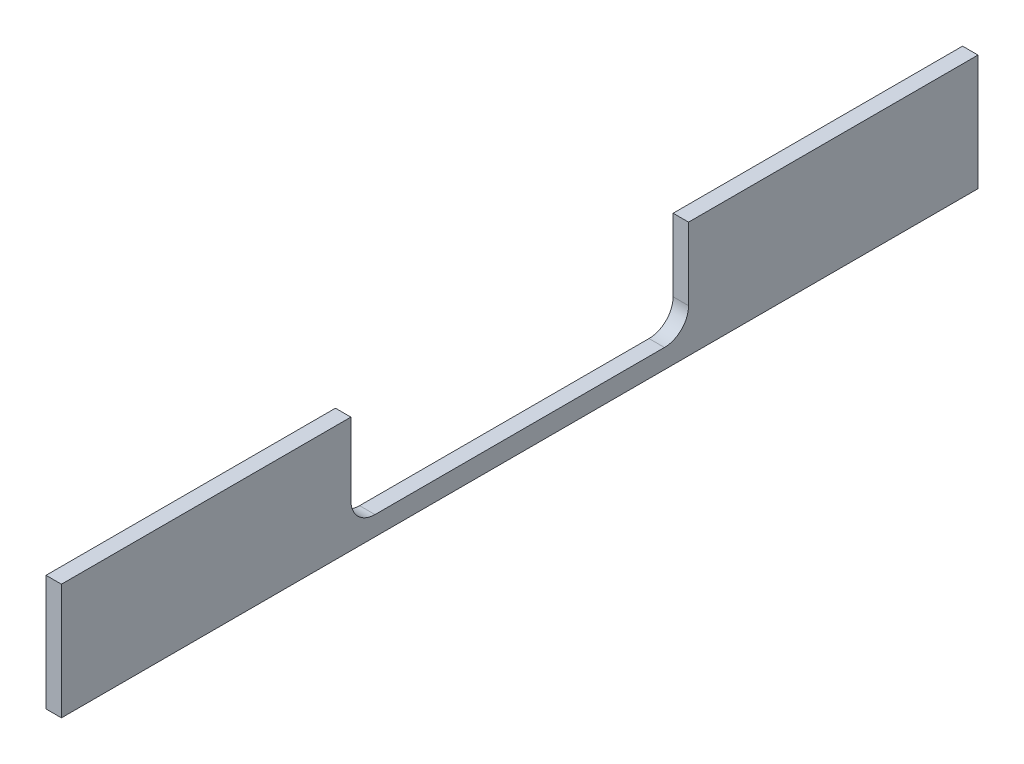
SolidWorks part; units mm, degrees
material "Balsa"
ref_plane "Front Plane" through (0, 0, 0) normal (0, 0, 1) x (1, 0, 0)
ref_plane "Top Plane" through (0, 0, 0) normal (0, 1, 0) x (1, 0, 0)
ref_plane "Right Plane" through (0, 0, 0) normal (1, 0, 0) x (0, 0, -1)
sketch "Sketch1" plane through (0, 0, 0) normal (1, 0, 0) x (0, 0, -1)
  line L1 (0, 0) -> (190, 0)
  line L2 (0, 0) -> (0, 24)
  line L3 (0, 24) -> (190, 24)
  line L4 (190, 0) -> (190, 24)
  dimension "D1" = 24
  dimension "D2" = 190
extrude "Boss-Extrude1" add sketch "Sketch1" along normal blind 3.2
sketch "Sketch2" plane through (0, 0, 0) normal (-1, 0, 0) x (0, 0, 1)
  line L0 (-95, 24) -> (-95, 4)
  line L3 (-190, 24) -> (0, 24) construction
  line L4 (-130, 24) -> (-130, 4)
  line L5 (-60, 24) -> (-60, 4)
  line L6 (-130, 4) -> (-60, 4)
  line L7 (-130, 24) -> (-60, 24)
  line M3 (0, 24) -> (-190, 24)
  dimension "D1" = 20
  dimension "D2" = 35
  dimension "D3" = 35
extrude "Cut-Extrude1" cut sketch "Sketch2" against normal blind 10 contours L4 L6 L0 M3 | L0 L6 L5 M3 region at (0, 14, -77.5) region at (0, 14, -112.5)
fillet "Fillet1" radius 5 2 edges at (1.6, 4, -60) (1.6, 4, -130)
